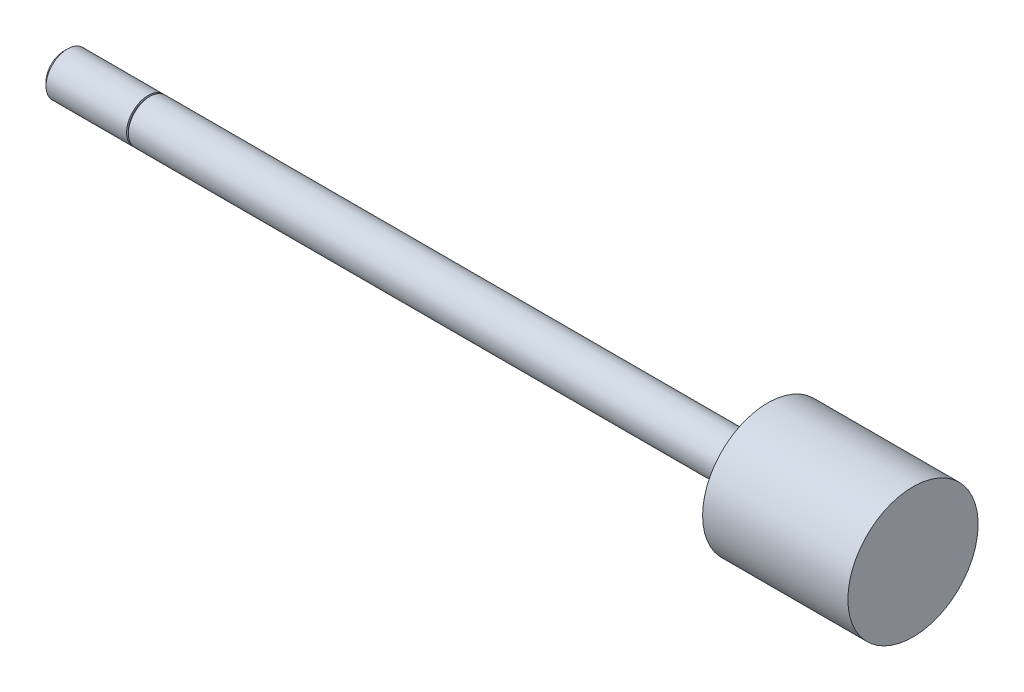
SolidWorks part; units mm, degrees
material "Plain Carbon Steel"
ref_plane "Front Plane" through (0, 0, 0) normal (0, 0, 1) x (1, 0, 0)
ref_plane "Top Plane" through (0, 0, 0) normal (0, 1, 0) x (1, 0, 0)
ref_plane "Right Plane" through (0, 0, 0) normal (1, 0, 0) x (0, 0, -1)
sketch "Sketch1" plane through (0, 0, 0) normal (0, 0, 1) x (1, 0, 0)
  line L0 (0, 0) -> (0, 3.175)
  line L1 (0, 3.175) -> (91.2876, 3.175)
  line L2 (91.2876, 3.175) -> (91.2876, 9.6203)
  line L3 (91.2876, 9.6203) -> (112.7506, 9.6203)
  line L4 (112.7506, 9.6203) -> (112.7506, 0)
  line L5 (112.7506, 0) -> (0, 0)
  line L6 (112.7506, 0) -> (0, 0) construction
revolve "Revolve1" add sketch "Sketch1" angle 360 about L6 reverse direction yes
cosmetic thread "Cosmetic Thread1" parameters "D1"=12.7, "D2"=5.268
sketch "Sketch2" plane through (0, 0, 0) normal (0, 0, 1) x (1, 0, 0)
  line L0 (-12.7, 0) -> (-12.7, 2.634)
  line L1 (-12.7, 2.634) -> (-12.159, 3.175)
  line L2 (-12.159, 3.175) -> (0, 3.175)
  line L3 (0, 3.175) -> (0, 0)
  line L4 (0, 0) -> (-12.7, 0)
  line L5 (0, 0) -> (-12.7, 0) construction
revolve "Revolve2" add sketch "Sketch2" angle 360 about L5 reverse direction yes
ref_plane "Plane1" through (0, 0, 0) normal (1, 0, 0) x (0, 0, -1)
ref_plane "Plane2" through (0, 0, 0) normal (1, 0, 0) x (0, 0, -1)
ref_plane "Plane3" through (204.0382, 0, 0) normal (1, 0, 0) x (0, 0, -1)
ref_plane "Plane4" through (-12.7, 0, 0) normal (1, 0, 0) x (0, 0, -1)
sketch "Sketch3" plane through (0, 0, 0) normal (0, 0, 1) x (1, 0, 0)
  line L0 (-0.254, 3.429) -> (-0.254, 2.921)
  line L1 (-0.254, 2.921) -> (0, 2.921)
  line L2 (0, 2.921) -> (0, 3.429)
  line L3 (0, 3.429) -> (-0.254, 3.429)
  line L4 (0, 0) -> (-0.254, 0) construction
revolve "Cut-Revolve1" cut sketch "Sketch3" angle 360 about L4 reverse direction yes
ref_plane "Plane5" through (0, 0, 0) normal (1, 0, 0) x (0, 0, -1)
ref_plane "Plane6" through (0, 0, 0) normal (1, 0, 0) x (0, 0, -1)
ref_plane "Plane7" through (-16.764, 0, 0) normal (1, 0, 0) x (0, 0, -1)
ref_plane "dia1 XY" through (0, 0, 0) normal (1, 0, 0) x (0, 0, -1)
ref_plane "dia1 XZ" through (0, 3.175, 0) normal (0, -1, 0) x (-1, 0, 0)
ref_plane "dia1 YZ" through (0, 0, 0) normal (0, 0, -1) x (-1, 0, 0)
ref_axis "dia1 X" through (0, 3.175, 80.9) along (0, 0, -1)
ref_axis "dia1 Y" through (0, -50, 0) along (0, 1, 0)
ref_axis "dia1 Z" through (80.9, 3.175, 0) along (-1, 0, 0)
sketch3d "dia1"
  point P0 (0, 3.175, 0)
ref_plane "dia12 XY" through (0, 0, 0) normal (1, 0, 0) x (0, 0, -1)
ref_plane "dia12 XZ" through (0, 0, 0) normal (0, -1, 0) x (-1, 0, 0)
ref_plane "dia12 YZ" through (0, 0, 10.9537) normal (0, 0, -1) x (-1, 0, 0)
ref_axis "dia12 X" through (0, 0, 80.9) along (0, 0, -1)
ref_axis "dia12 Y" through (0, -50, 10.9537) along (0, 1, 0)
ref_axis "dia12 Z" through (80.9, 0, 10.9537) along (-1, 0, 0)
sketch3d "dia12"
  point P0 (0, 0, 10.9537)
ref_plane "dia1r XY" through (0, 0, 0) normal (1, 0, 0) x (0, 0, -1)
ref_plane "dia1r XZ" through (0, 0, 0) normal (0, -1, 0) x (-1, 0, 0)
ref_plane "dia1r YZ" through (0, 0, 10.2235) normal (0, 0, -1) x (-1, 0, 0)
ref_axis "dia1r X" through (0, 0, 80.9) along (0, 0, -1)
ref_axis "dia1r Y" through (0, -50, 10.2235) along (0, 1, 0)
ref_axis "dia1r Z" through (80.9, 0, 10.2235) along (-1, 0, 0)
sketch3d "dia1r"
  point P0 (0, 0, 10.2235)
ref_plane "dia2 XY" through (0, 0, 0) normal (1, 0, 0) x (0, 0, -1)
ref_plane "dia2 XZ" through (0, -3.175, 0) normal (0, -1, 0) x (-1, 0, 0)
ref_plane "dia2 YZ" through (0, 0, 0) normal (0, 0, -1) x (-1, 0, 0)
ref_axis "dia2 X" through (0, -3.175, 80.9) along (0, 0, -1)
ref_axis "dia2 Y" through (0, -50, 0) along (0, 1, 0)
ref_axis "dia2 Z" through (80.9, -3.175, 0) along (-1, 0, 0)
sketch3d "dia2"
  point P0 (0, -3.175, 0)
ref_plane "dia22 XY" through (0, 0, 0) normal (1, 0, 0) x (0, 0, -1)
ref_plane "dia22 XZ" through (0, 0, 0) normal (0, -1, 0) x (-1, 0, 0)
ref_plane "dia22 YZ" through (0, 0, -10.9537) normal (0, 0, -1) x (-1, 0, 0)
ref_axis "dia22 X" through (0, 0, 80.9) along (0, 0, -1)
ref_axis "dia22 Y" through (0, -50, -10.9537) along (0, 1, 0)
ref_axis "dia22 Z" through (80.9, 0, -10.9537) along (-1, 0, 0)
sketch3d "dia22"
  point P0 (0, 0, -10.9537)
ref_plane "dia2r XY" through (0, 0, 0) normal (1, 0, 0) x (0, 0, -1)
ref_plane "dia2r XZ" through (0, 0, 0) normal (0, -1, 0) x (-1, 0, 0)
ref_plane "dia2r YZ" through (0, 0, -10.2235) normal (0, 0, -1) x (-1, 0, 0)
ref_axis "dia2r X" through (0, 0, 80.9) along (0, 0, -1)
ref_axis "dia2r Y" through (0, -50, -10.2235) along (0, 1, 0)
ref_axis "dia2r Z" through (80.9, 0, -10.2235) along (-1, 0, 0)
sketch3d "dia2r"
  point P0 (0, 0, -10.2235)
ref_plane "rl1 XY" through (-12.7, 0, 0) normal (1, 0, 0) x (0, 0, -1)
ref_plane "rl1 XZ" through (0, 0, 0) normal (0, -1, 0) x (-1, 0, 0)
ref_plane "rl1 YZ" through (0, 0, 0) normal (0, 0, -1) x (-1, 0, 0)
ref_axis "rl1 X" through (-12.7, 0, 80.9) along (0, 0, -1)
ref_axis "rl1 Y" through (-12.7, -50, 0) along (0, 1, 0)
ref_axis "rl1 Z" through (80.9, 0, 0) along (-1, 0, 0)
sketch3d "rl1"
  point P0 (-12.7, 0, 0)
ref_plane "rl2 XY" through (0, 0, 0) normal (1, 0, 0) x (0, 0, -1)
ref_plane "rl2 XZ" through (0, 0, 0) normal (0, -1, 0) x (-1, 0, 0)
ref_plane "rl2 YZ" through (0, 0, 0) normal (0, 0, -1) x (-1, 0, 0)
ref_axis "rl2 X" through (0, 0, 80.9) along (0, 0, -1)
ref_axis "rl2 Y" through (0, -50, 0) along (0, 1, 0)
ref_axis "rl2 Z" through (80.9, 0, 0) along (-1, 0, 0)
sketch3d "rl2"
  point P0 (0, 0, 0)
ref_plane "rod_cp XY" through (0, 0, 0) normal (1, 0, 0) x (0, 0, -1)
ref_plane "rod_cp XZ" through (0, 0, 0) normal (0, -1, 0) x (-1, 0, 0)
ref_plane "rod_cp YZ" through (0, 0, 0) normal (0, 0, -1) x (-1, 0, 0)
ref_axis "rod_cp X" through (0, 0, 80.9) along (0, 0, -1)
ref_axis "rod_cp Y" through (0, -50, 0) along (0, 1, 0)
ref_axis "rod_cp Z" through (80.9, 0, 0) along (-1, 0, 0)
sketch3d "rod_cp"
  point P0 (0, 0, 0)
ref_plane "thd1 XY" through (-12.7, 0, 0) normal (1, 0, 0) x (0, 0, -1)
ref_plane "thd1 XZ" through (0, 3.175, 0) normal (0, -1, 0) x (-1, 0, 0)
ref_plane "thd1 YZ" through (0, 0, 0) normal (0, 0, -1) x (-1, 0, 0)
ref_axis "thd1 X" through (-12.7, 3.175, 80.9) along (0, 0, -1)
ref_axis "thd1 Y" through (-12.7, -50, 0) along (0, 1, 0)
ref_axis "thd1 Z" through (80.9, 3.175, 0) along (-1, 0, 0)
sketch3d "thd1"
  point P0 (-12.7, 3.175, 0)
ref_plane "thd2 XY" through (-12.7, 0, 0) normal (1, 0, 0) x (0, 0, -1)
ref_plane "thd2 XZ" through (0, -3.175, 0) normal (0, -1, 0) x (-1, 0, 0)
ref_plane "thd2 YZ" through (0, 0, 0) normal (0, 0, -1) x (-1, 0, 0)
ref_axis "thd2 X" through (-12.7, -3.175, 80.9) along (0, 0, -1)
ref_axis "thd2 Y" through (-12.7, -50, 0) along (0, 1, 0)
ref_axis "thd2 Z" through (80.9, -3.175, 0) along (-1, 0, 0)
sketch3d "thd2"
  point P0 (-12.7, -3.175, 0)
ref_plane "to_rod_clevis XY" through (-16.764, 0, 0) normal (1, 0, 0) x (0, 0, -1)
ref_plane "to_rod_clevis XZ" through (0, 0, 0) normal (0, -1, 0) x (-1, 0, 0)
ref_plane "to_rod_clevis YZ" through (0, 0, 0) normal (0, 0, -1) x (-1, 0, 0)
ref_axis "to_rod_clevis X" through (-16.764, 0, 80.9) along (0, 0, -1)
ref_axis "to_rod_clevis Y" through (-16.764, -50, 0) along (0, 1, 0)
ref_axis "to_rod_clevis Z" through (80.9, 0, 0) along (-1, 0, 0)
sketch3d "to_rod_clevis"
  point P0 (-16.764, 0, 0)
